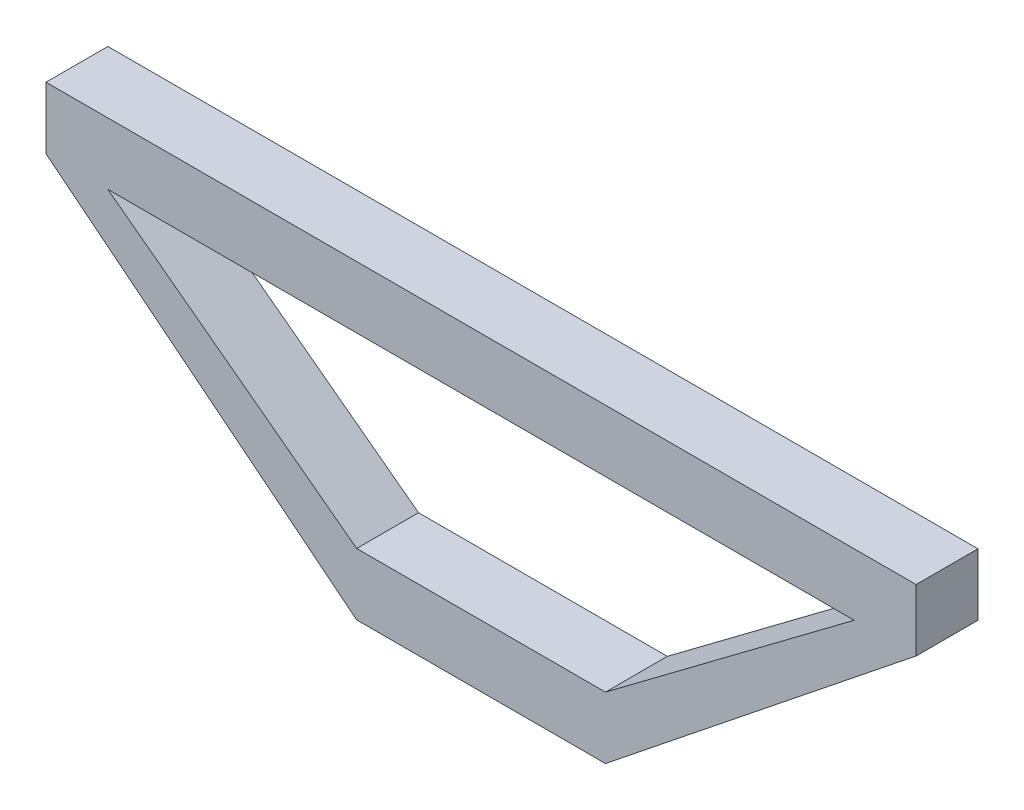
SolidWorks part; units mm, degrees
material "Alloy Steel"
ref_plane "Front Plane" through (0, 0, 0) normal (0, 0, 1) x (1, 0, 0)
ref_plane "Top Plane" through (0, 0, 0) normal (0, 1, 0) x (1, 0, 0)
ref_plane "Right Plane" through (0, 0, 0) normal (1, 0, 0) x (0, 0, -1)
sketch "Sketch1" plane through (0, 0, 0) normal (0, 0, 1) x (1, 0, 0)
  line L0 (0, 0) -> (400, 0)
  line L3 (400, 0) -> (800, 300)
  line L4 (-400, 300) -> (800, 300)
  line L5 (0, 0) -> (-400, 300)
  line L6 (-499.5, 399.5) -> (899.5, 399.5)
  line L9 (899.5, 399.5) -> (899.5, 300)
  line L11 (400, -99.5) -> (899.5, 300)
  line L14 (0, -99.5) -> (400, -99.5)
  line L16 (0, -99.5) -> (-499.5, 300)
  line L17 (-499.5, 300) -> (-499.5, 399.5)
  point P3 (0, 0)
  point P7 (0, 0)
  point P8 (0, 0)
extrude "Boss-Extrude3" add sketch "Sketch1" along normal blind 99.5 contours L6 L9 L11 L14 L16 L17
extrude "Cut-Extrude2" cut sketch "Sketch1<10>" along normal through all flip side to cut
sketch "Sketch1<10>" plane through (0, 0, 0) normal (0, 0, 1) x (1, 0, 0) same geometry as "Sketch1"
